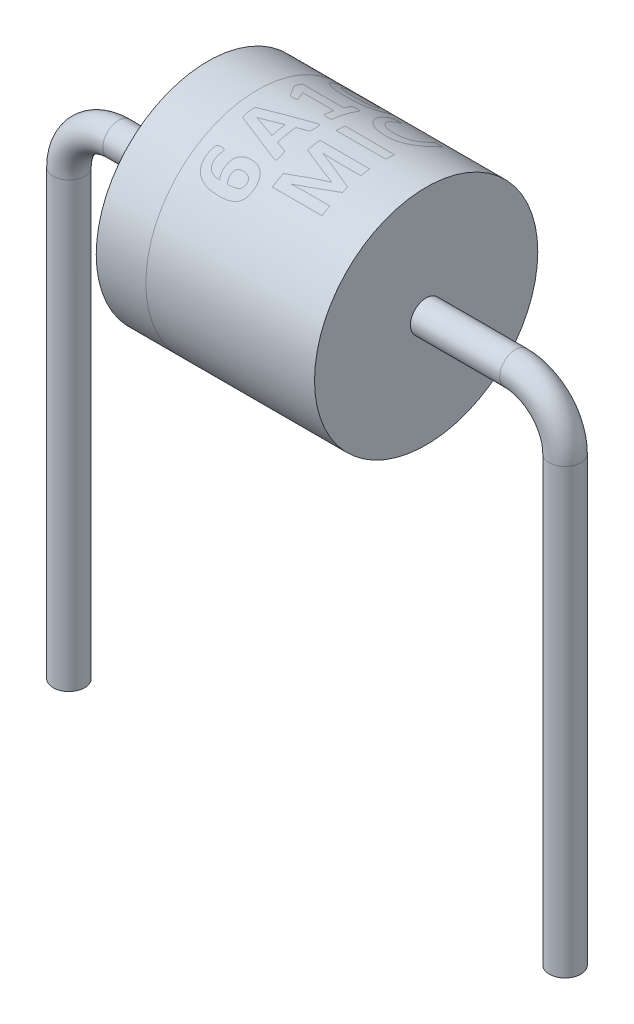
SolidWorks part; units mm, degrees
other "Wire"
other "Cathode Silver Band"
other "Diode"
ref_plane "Front Plane" through (0, 0, 0) normal (0, 0, 1) x (1, 0, 0)
ref_plane "Top Plane" through (0, 0, 0) normal (0, 1, 0) x (1, 0, 0)
ref_plane "Right Plane" through (0, 0, 0) normal (1, 0, 0) x (0, 0, -1)
sketch "Sketch1" plane through (0, 0, 0) normal (1, 0, 0) x (0, 0, -1)
  circle A0 centre (0, 0) radius 4.5
  circle A1 centre (0, 0) radius 0.635
  dimension "D1" = 9
  dimension "D2" = 1.27
extrude "Boss-Extrude1" add sketch "Sketch1" along normal mid plane 8.8
sketch "Sketch2" plane through (-4.4, 0, 0) normal (-1, 0, 0) x (0, 0, 1)
  circle A1 centre (0, 0) radius 4.5 construction
  circle A2 centre (0, 0) radius 4.49
  circle A3 centre (0, 0) radius 4.49
  circle A4 centre (0, 0) radius 4.5
  dimension "D1" = 0.01
extrude "Cut-Extrude1" cut sketch "Sketch2" against normal blind 2
sketch "Sketch3" plane through (-2.4, 0, 0) normal (-1, 0, 0) x (0, 0, 1)
  circle A0 centre (0, 0) radius 4.49 construction
  circle A1 centre (0, 0) radius 4.49
  circle A2 centre (0, 0) radius 4.5 construction
  circle A3 centre (0, 0) radius 4.5
extrude "Boss-Extrude2" add sketch "Sketch3" along normal up to surface (2 mm away) separate body up to face at (-4.4, 0, -0.635)
ref_plane "Plane1" through (0, 5, 0) normal (0, 1, 0) x (1, 0, 0)
sketch "Sketch4" plane through (0, 5, 0) normal (0, 1, 0) x (1, 0, 0)
  line L0 (0.1, 7.5) -> (0.1, -7.5) construction
  line L1 (0.1, 0) -> (-4.4, 0) construction
  line L2 (-4.4, 4.5) -> (-4.4, -4.5) construction
  line L4 (0.1, 0) -> (2.6, 0) construction
  line L5 (2.6, 7.5) -> (2.6, -7.5) construction
  text T0 "6A10" font "Calibri" height 2
  text T1 "MIC" font "Corbel" height 2
  dimension "D1" = 4.5
  dimension "D2" = 15
  dimension "D3" = 2.5
wrap "Wrap1" sketch "Sketch4" wrap type scribe source sketch "Sketch4" face at (4.4, 0, -4.5)
sketch "Sketch5" plane through (0, 0, 0) normal (0, 0, 1) x (1, 0, 0)
  line L0 (0, 0) -> (-8, 0)
  line L1 (-10, -2) -> (-10, -19.8584)
  line L2 (0, 0) -> (8, 0)
  line L3 (10, -2) -> (10, -19.8584)
  arc A0 (-8, 0) -> (-10, -2) centre (-8, -2) ccw
  arc A1 (8, 0) -> (10, -2) centre (8, -2) cw
  dimension "D2" = 2
  dimension "D3" = 58
  dimension "D1" = 20
sketch "Sketch6" plane through (0, 0, 0) normal (1, 0, 0) x (0, 0, -1)
  circle A0 centre (0, 0) radius 0.635
  dimension "D1" = 1.27
sweep "Sweep1" add profiles "Sketch6" path "Sketch5"
